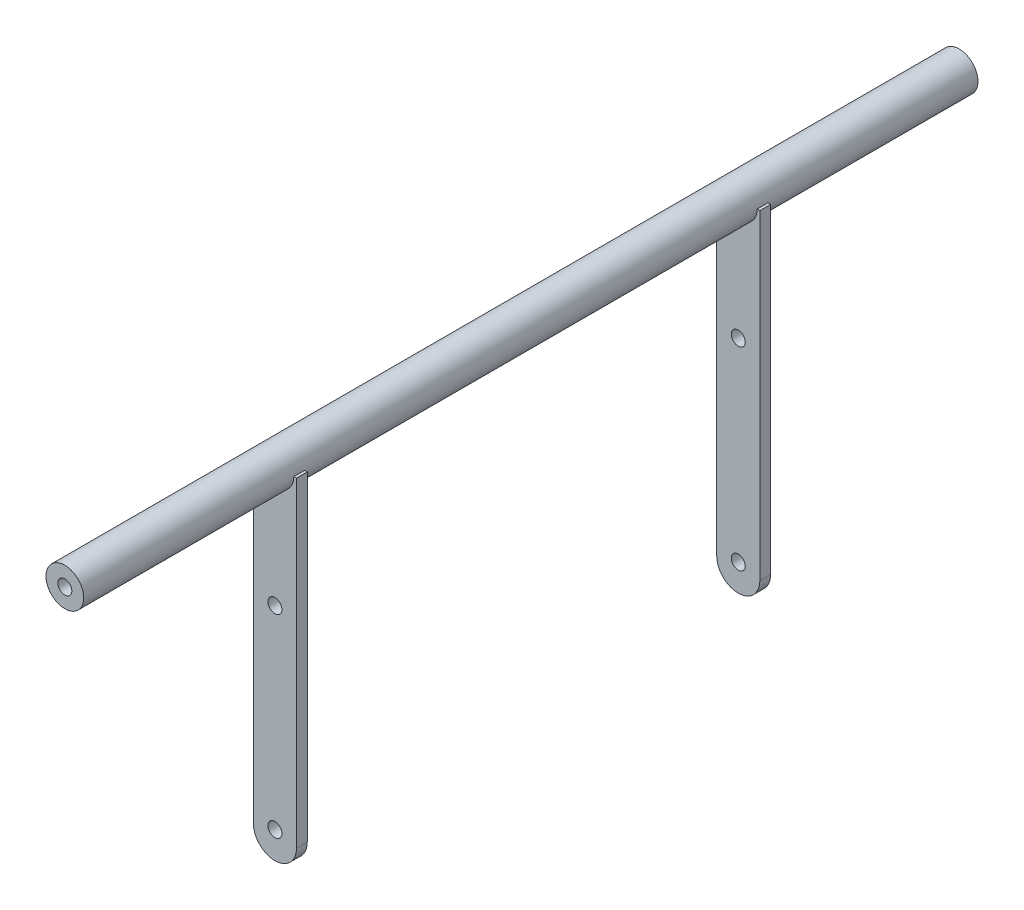
SolidWorks part; units mm, degrees
ref_plane "Front Plane" through (0, 0, 0) normal (0, 0, 1) x (1, 0, 0)
ref_plane "Top Plane" through (0, 0, 0) normal (0, 1, 0) x (1, 0, 0)
ref_plane "Right Plane" through (0, 0, 0) normal (1, 0, 0) x (0, 0, -1)
sketch "Sketch1" plane through (0, 0, 0) normal (0, 0, 1) x (1, 0, 0)
  circle A0 centre (0, 0) radius 17.5
  dimension "D1" = 35
extrude "Boss-Extrude1" add sketch "Sketch1" along normal mid plane 830
sketch "Sketch2" plane through (0, 0, 415) normal (0, 0, 1) x (1, 0, 0)
  circle A0 centre (0, 0) radius 6.5
  dimension "D1" = 13
extrude "Cut-Extrude1" cut sketch "Sketch2" against normal up to next
sketch "Sketch3" plane through (0, 0, 0) normal (1, 0, 0) x (0, 0, -1)
  line L0 (-415, 0) -> (415, 0) construction
  line L1 (-415, 17.5) -> (-415, -17.5) construction
  line L2 (415, -17.5) -> (415, 17.5) construction
  line L3 (0, 301.5209) -> (0, -360.8541) construction
  line L4 (-220, 0) -> (-210, 0)
  line L5 (-220, 0) -> (-220, -317.5)
  line L6 (-220, -317.5) -> (-210, -317.5)
  line L7 (-210, 0) -> (-210, -317.5)
  line L8 (-415, -17.5) -> (415, -17.5) construction
  line L9 (210, 0) -> (210, -317.5)
  line L10 (220, -317.5) -> (210, -317.5)
  line L11 (220, 0) -> (220, -317.5)
  line L12 (220, 0) -> (210, 0)
  dimension "D1" = 440
  dimension "D2" = 10
  dimension "D3" = 300
extrude "Boss-Extrude2" add sketch "Sketch3" along normal mid plane 40
fillet "Fillet1" radius 20 4 edges at (-20, -317.5, -215) (20, -317.5, -215) (-20, -317.5, 215) (20, -317.5, 215)
sketch "Sketch4" plane through (0, 0, 220) normal (0, 0, 1) x (1, 0, 0)
  line L0 (0, 28.7761) -> (0, -317.5) construction
  circle A0 centre (0, -292.5) radius 6.5
  circle A1 centre (0, -112.5) radius 6.5
  dimension "D1" = 13
  dimension "D3" = 180
  dimension "D2" = 25
extrude "Cut-Extrude2" cut sketch "Sketch4" against normal blind 542
